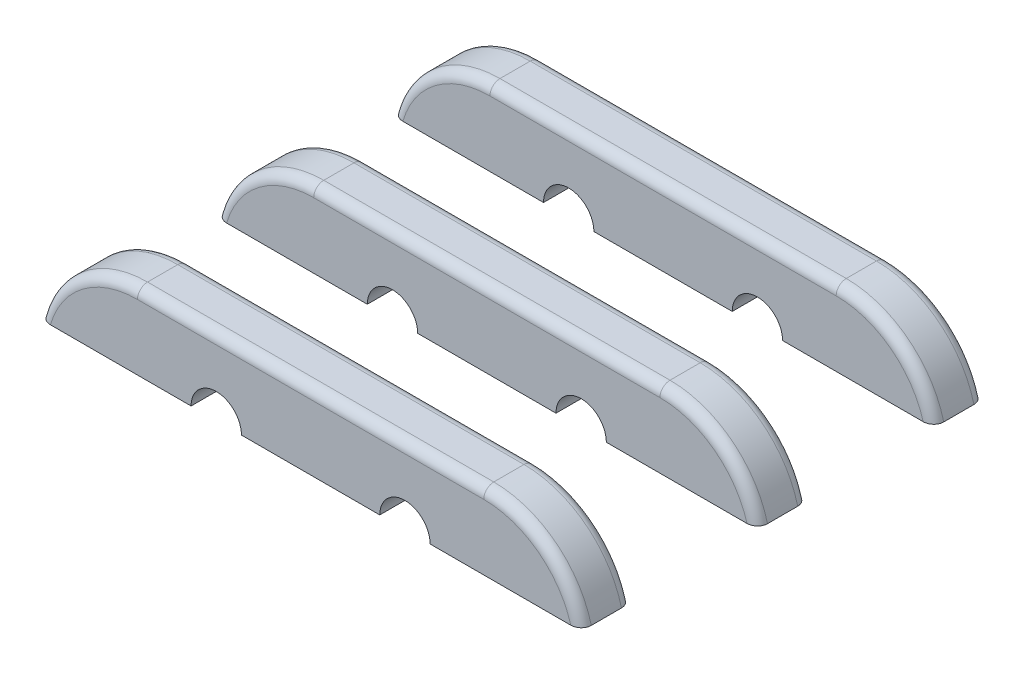
SolidWorks part; units mm, degrees
ref_plane "Front Plane" through (0, 0, 0) normal (0, 0, 1) x (1, 0, 0)
ref_plane "Top Plane" through (0, 0, 0) normal (0, 1, 0) x (1, 0, 0)
ref_plane "Right Plane" through (0, 0, 0) normal (1, 0, 0) x (0, 0, -1)
sketch "Sketch1" plane through (0, 0, 0) normal (0, 1, 0) x (1, 0, 0)
  line L1 (-9.75, -14.75) -> (9.75, -14.75)
  line L2 (-9.75, -14.75) -> (-9.75, 14.75)
  line L3 (-9.75, 14.75) -> (9.75, 14.75)
  line L4 (9.75, -14.75) -> (9.75, 14.75)
  line L5 (-9.75, -14.75) -> (9.75, 14.75) construction
  line L6 (-9.75, 14.75) -> (9.75, -14.75) construction
  point P0 (0, 0)
  dimension "D1" = 19.5
  dimension "D2" = 29.5
extrude "Boss-Extrude1" add sketch "Sketch1" along normal blind 4 contours L2 L1 L4 L3
sketch "Sketch2" plane through (0, 4, 0) normal (0, 1, 0) x (1, 0, 0)
  line L1 (-30, -20) -> (30, -20)
  line L2 (-30, -20) -> (-30, 20)
  line L3 (-30, 20) -> (30, 20)
  line L4 (30, -20) -> (30, 20)
  line L5 (-30, -20) -> (30, 20) construction
  line L6 (-30, 20) -> (30, -20) construction
  point P0 (0, 0)
  dimension "D1" = 60
  dimension "D2" = 40
extrude "Boss-Extrude3" add sketch "Sketch2" along normal blind 4
sketch "Sketch3" plane through (0, 8, 0) normal (0, 1, 0) x (1, 0, 0)
  line L0 (30, -20) -> (30, 20) construction
  line L1 (-30, 20) -> (30, 20)
  line L2 (-30, 20) -> (-30, 15)
  line L3 (-30, 15) -> (30, 15)
  line L4 (30, 20) -> (30, 15)
  line L6 (30, -20) -> (30, -15)
  line L7 (-30, -15) -> (30, -15)
  line L8 (-30, -20) -> (-30, -15)
  line L9 (-30, -20) -> (30, -20)
  line M9 (30, -20) -> (30, 20)
  line M10 (30, 20) -> (-30, 20)
  line M11 (-30, 20) -> (-30, -20)
  dimension "D1" = 5
extrude "Boss-Extrude4" add sketch "Sketch3" along normal blind 20 contours L3 M11 M9 M10 | L6 L7 L8 L9 region at (0, 8, -17.5)
chamfer "Chamfer1" distance 5 distance2 20 1 edges at (-30, 28, 17.5) first distance on face at (0, 28, 17.5)
chamfer "Chamfer2" distance 20 distance2 5 1 edges at (-30, 28, -17.5) first distance on face at (-30, 12.5714, -2.1429)
chamfer "Chamfer3" distance 20 distance2 5 2 edges at (30, 28, -17.5) (30, 28, 17.5) first distance on face at (30, 17, 0)
fillet "Fillet1" radius 10 4 edges at (25, 28, 17.5) (25, 28, -17.5) (-25, 28, 17.5) (-25, 28, -17.5)
fillet "Fillet2" radius 1 10 edges at (28.4468, 14.2127, -20) (23.3464, 25.8821, -20) (-28.4468, 14.2127, -20) (-23.3464, 25.8821, -20) (-28.4468, 14.2127, 20) (-23.3464, 25.8821, 20) (28.4468, 14.2127, 20) (23.3464, 25.8821, 20) (0, 28, -20) (0, 28, 20)
sketch "Sketch4" plane through (0, 8, 0) normal (0, 1, 0) x (1, 0, 0)
  line L0 (30, -15) -> (30, 15) construction
  line L1 (-30, 2.5) -> (30, 2.5)
  line L2 (-30, 2.5) -> (-30, -2.5)
  line L3 (-30, -2.5) -> (30, -2.5)
  line L4 (30, 2.5) -> (30, -2.5)
  line L5 (-30, 2.5) -> (30, -2.5) construction
  line L6 (-30, -2.5) -> (30, 2.5) construction
  point P0 (0, 0)
  dimension "D1" = 5
extrude "Boss-Extrude5" add sketch "Sketch4" along normal blind 20
chamfer "Chamfer4" distance 20 distance2 5 2 edges at (30, 28, 0) (-30, 28, 0) first distance on face at (30, 11.3671, 0) first distance on face at (-30, 11.3671, 0)
fillet "Fillet3" radius 10 2 edges at (-25, 28, 0) (25, 28, 0)
fillet "Fillet4" radius 1 10 edges at (28.4468, 14.2127, -2.5) (23.3464, 25.8821, -2.5) (-28.4468, 14.2127, -2.5) (-23.3464, 25.8821, -2.5) (-28.4468, 14.2127, 2.5) (-23.3464, 25.8821, 2.5) (28.4468, 14.2127, 2.5) (23.3464, 25.8821, 2.5) (0, 28, -2.5) (0, 28, 2.5)
fillet "Fillet5" radius 1 10 edges at (-28.4468, 14.2127, 15) (-23.3464, 25.8821, 15) (28.4468, 14.2127, 15) (23.3464, 25.8821, 15) (-28.4468, 14.2127, -15) (-23.3464, 25.8821, -15) (28.4468, 14.2127, -15) (23.3464, 25.8821, -15) (0, 28, 15) (0, 28, -15)
sketch "Sketch5" plane through (0, 0, 20) normal (0, 0, 1) x (1, 0, 0)
  line L0 (17.1922, 27) -> (-17.1922, 27) construction
  circle A0 centre (-9.3692, 20.5) radius 2.5
  circle A1 centre (9.3692, 20.5) radius 2.5
  dimension "D1" = 6.5
  dimension "D2" = 20.6
extrude "Cut-Extrude1" cut sketch "Sketch5" against normal through all contours A0 | A1
sketch "Sketch6" plane through (0, 0, 0) normal (0, 1, 0) x (1, 0, 0)
  line L1 (31.7055, 21.6056) -> (-31.7055, 21.6056)
  line L2 (31.7055, 21.6056) -> (31.7055, -21.6056)
  line L3 (31.7055, -21.6056) -> (-31.7055, -21.6056)
  line L4 (-31.7055, 21.6056) -> (-31.7055, -21.6056)
  line L5 (31.7055, 21.6056) -> (-31.7055, -21.6056) construction
  line L6 (31.7055, -21.6056) -> (-31.7055, 21.6056) construction
  point P0 (0, 0)
extrude "Cut-Extrude3" cut sketch "Sketch6" along normal blind 20.5
